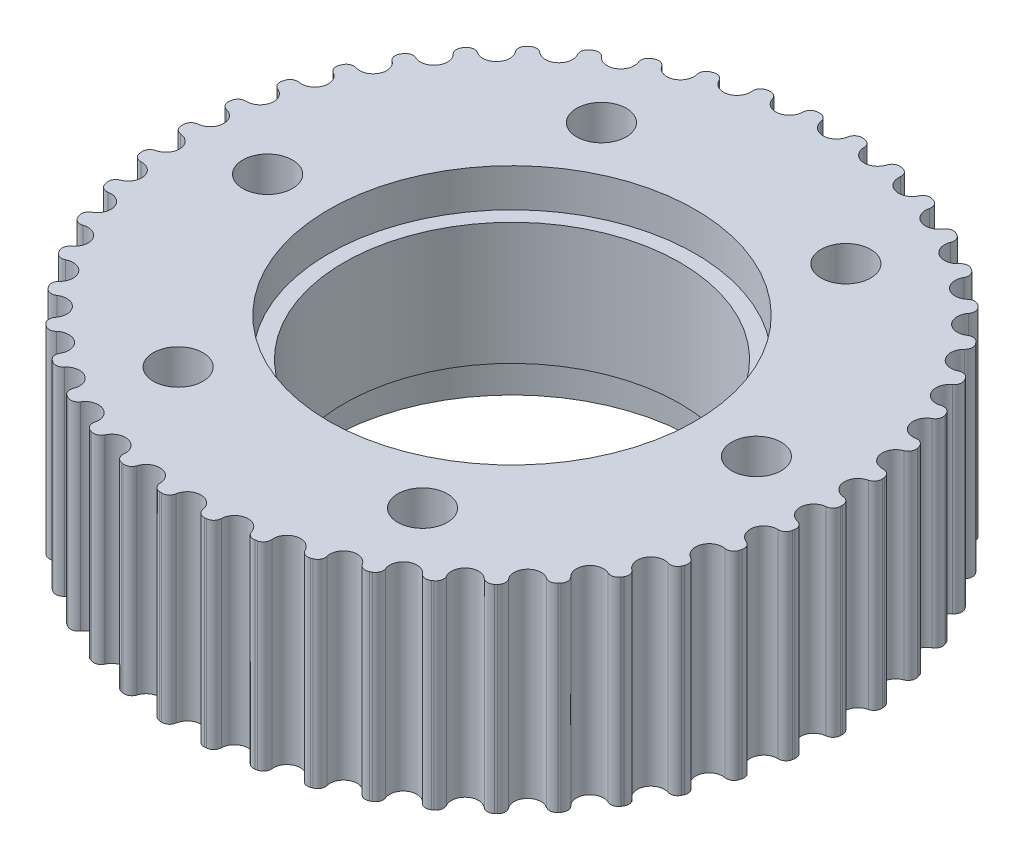
SolidWorks part; units mm, degrees
ref_plane "Front Plane" through (0, 0, 0) normal (0, 0, 1) x (1, 0, 0)
ref_plane "Top Plane" through (0, 0, 0) normal (0, 1, 0) x (1, 0, 0)
ref_plane "Right Plane" through (0, 0, 0) normal (1, 0, 0) x (0, 0, -1)
sketch "Sketch1" plane through (0, 0, 0) normal (0, 1, 0) x (1, 0, 0)
  line L0 (0, 0) -> (0, 21.582) construction
  line L1 (0, 0) -> (2.8938, 21.0541) construction
  circle A0 centre (0, 0) radius 21.582 construction
  circle A1 centre (0, 0) radius 20.362 construction
  circle A2 centre (0, 21.252) radius 0.89 construction
  circle A5 centre (2.8938, 21.0541) radius 0.89 construction
  arc A6 (0, 20.362) -> (0.8793, 21.1145) centre (0, 21.252) ccw
  arc A7 (0.8793, 21.1145) -> (1.4059, 21.5362) centre (1.3733, 21.0373) cw
  arc A8 (1.5397, 21.527) -> (2.004, 21.0376) centre (1.5041, 21.0283) cw
  arc A9 (2.7726, 20.1724) -> (2.004, 21.0376) centre (2.8938, 21.0541) cw
  arc A10 (1.4059, 21.5362) -> (1.5397, 21.527) centre (0, 0) cw
  arc A11 (0, 20.362) -> (2.7726, 20.1724) centre (0, 0) ccw
  dimension "D1" = 43.1641
  dimension "D3" = 1.78
  dimension "D4" = 0.5
  dimension "D2" = 1.22
  dimension "D5" = 7.826
extrude "Boss-Extrude1" add sketch "Sketch1" along normal mid plane 13 contours A6 A11 A9 A8 A7 region at (0.0017, 0, -0.025)
ref_axis "Axis1" through (0, 3.3, 0) along (0, -1, 0)
pattern_circular "CirPattern1" count 46 over 360 about axis through (0, 3.3, 0) along (0, -1, 0) of "Boss-Extrude1"
sketch "Sketch2" plane through (0, 0, 0) normal (1, 0, 0) x (0, 0, -1)
  line L10 (0, 6.5) -> (22.7568, 6.5) construction
  line L11 (0, 6.5) -> (0, 8.0875) construction
  line L12 (0, 8.0875) -> (22.7568, 8.0875) construction
  line L15 (22.7568, 6.5) -> (22.7568, 8.0875) construction
  line L20 (0, 3.3) -> (0, -3.3) construction
  line L22 (22.7568, 8.0875) -> (0, 8.0875)
  line L23 (22.7568, 8.0875) -> (22.7568, 6.5)
  line L24 (22.7568, 6.5) -> (0, 6.5)
  line L25 (0, 8.0875) -> (0, 6.5)
  dimension "D1" = 1.5875
  dimension "D2" = 22.7568
  dimension "D3" = 6.5
revolve "Revolve3" [suppressed] add sketch "Sketch2" angle 360 about axis through (0, 3.3, 0) along (0, -1, 0)
mirror "Mirror1" [suppressed] about plane through (0, 0, 0) normal (0, 1, 0)
sketch "Sketch3" plane through (0, 0, 0) normal (0, -1, 0) x (-1, 0, 0)
  circle A0 centre (0, 0) radius 11
  dimension "D1" = 22
extrude "Cut-Extrude1" cut sketch "Sketch3" against normal through all both and the other way through all
sketch "Sketch4" plane through (0, 0, 0) normal (0, 1, 0) x (1, 0, 0)
  circle A0 centre (-16, 0) radius 1.625
  dimension "D1" = 3.25
extrude "Cut-Extrude2" cut sketch "Sketch4" against normal through all both and the other way through all
pattern_circular "CirPattern2" count 6 over 360 about axis through (0, 6.5, 0) along (0, -1, 0) of "Cut-Extrude2"
sketch "Sketch7" plane through (0, 0, 0) normal (0, 1, 0) x (1, 0, 0)
  circle A0 centre (0, 0) radius 12
  dimension "D1" = 24
extrude "Cut-Extrude3" cut sketch "Sketch7" along normal through all from offset 4
mirror "Mirror2" about plane through (0, 0, 0) normal (0, 1, 0) of "Cut-Extrude3"
equation "\"TEETH_NUM\"= 46"
equation "\"TOOTH_PITCH\"= 3mm"
equation "\"PITCH_LINE_OFFSET\"= .015in"
equation "\"DIAMETER_PER_GROOVE\"= \"OUTSIDE_DIAMETER\" / \"TEETH_NUM\" * 1in"
equation "\"PITCH_DIAMETER\"= ( ( \"TEETH_NUM\" * 3 - 1.31 ) / 3.1415 + .415 ) * 1mm"
equation "\"OUTSIDE_DIAMETER\"= \"PITCH_DIAMETER\" - \"PITCH_LINE_OFFSET\" * 2"
equation "\"D1@Sketch1\"=\"OUTSIDE_DIAMETER\""
equation "\"TOOTH_HEIGHT\"= 1.22mm"
equation "\"D2@Sketch1\"=\"TOOTH_HEIGHT\""
equation "\"TOOTH_DIAMETER\"= 1.78mm"
equation "\"INTERNAL_RADIUS\"= .5mm"
equation "\"D3@Sketch1\"=\"TOOTH_DIAMETER\""
equation "\"D5@Sketch1\"=360 / \"TEETH_NUM\""
equation "\"D4@Sketch1\"=\"INTERNAL_RADIUS\""
equation "\"D1@CirPattern1\"=\"TEETH_NUM\""
equation "\"BELT_GAP\"= 13mm"
equation "\"D2@Sketch2\"=\"PITCH_DIAMETER\"/2+1/32"
equation "\"D3@Sketch2\"=\"BELT_GAP\"/2"
equation "\"ID\"= \"bearing_OD\" - 2mm"
equation "\"D1@Sketch3\"=\"ID\""
equation "\"D1@Boss-Extrude1\"=\"BELT_GAP\""
equation "\"bearing_thickness\" = 5mm"
equation "\"Outside_Plate_Thickness\"= 2.5mm"
equation "\"Recess_Height\"= \"BELT_GAP\" / 2 + \"Outside_Plate_Thickness\" - \"bearing_thickness\""
equation "\"bearing_OD\"= 24mm"
equation "\"D1@Sketch7\"=\"bearing_OD\""
equation "\"D19@Cut-Extrude3\"=\"Recess_Height\""
